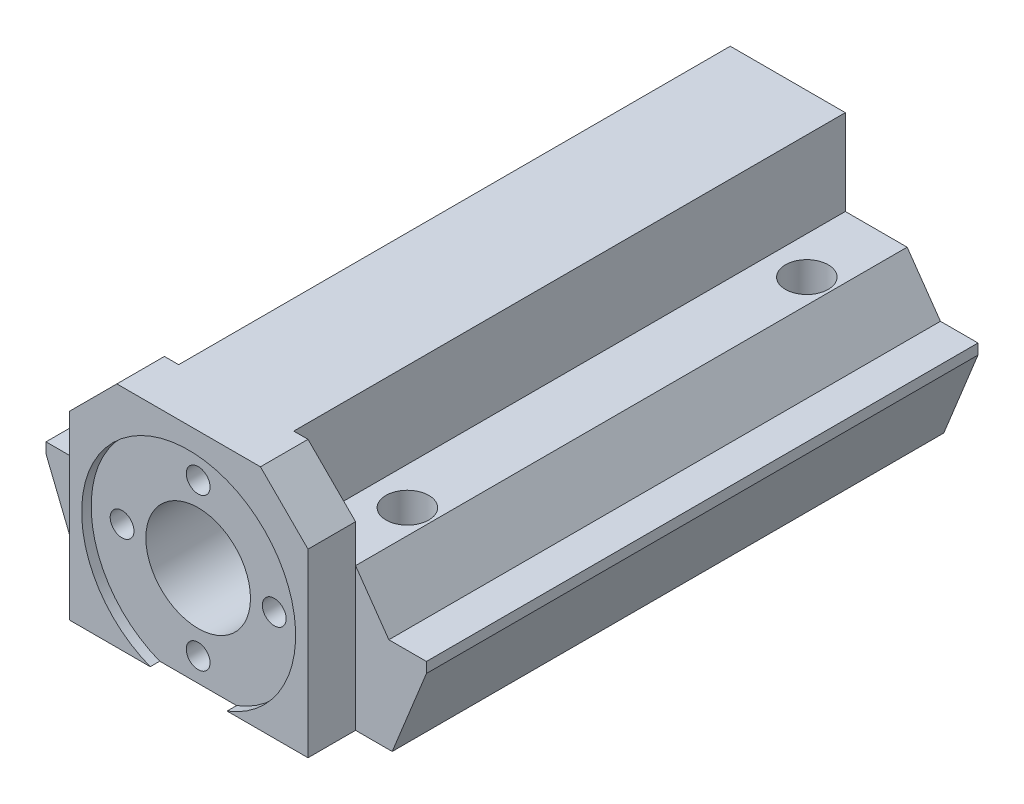
SolidWorks part; units mm, degrees
ref_plane "Front Plane" through (0, 0, 0) normal (0, 0, 1) x (1, 0, 0)
ref_plane "Top Plane" through (0, 0, 0) normal (0, 1, 0) x (1, 0, 0)
ref_plane "Right Plane" through (0, 0, 0) normal (1, 0, 0) x (0, 0, -1)
sketch "Sketch1" plane through (0, 0, 0) normal (0, 0, 1) x (1, 0, 0)
  line L0 (0, 0) -> (0, 14.7846) construction
  line L1 (-6.05, 25) -> (6.05, 25)
  line L2 (6.05, 25) -> (6.05, 16)
  line L3 (6.05, 16) -> (12.55, 16)
  line L4 (12.55, 16) -> (12.55, 0)
  line L5 (12.55, 0) -> (-12.55, 0)
  line L6 (-12.55, 16) -> (-12.55, 0)
  line L7 (-6.05, 16) -> (-12.55, 16)
  line L8 (-6.05, 25) -> (-6.05, 16)
  point P5 (0, 0)
  point P13 (0, 25)
  dimension "D1" = 12.1
  dimension "D2" = 6.5
  dimension "D3" = 16
  dimension "D4" = 9
extrude "Boss-Extrude1" add sketch "Sketch1" along normal blind 58
sketch "Sketch11" plane through (0, 0, 0) normal (0, 0, -1) x (-1, 0, 0)
  line L0 (-12.55, 0) -> (-12.55, 16) construction
  line L1 (-20, 11) -> (20, 11)
  line L2 (-20, 11) -> (-20, 0)
  line L3 (-20, 0) -> (20, 0)
  line L4 (20, 11) -> (20, 0)
  line L9 (12.55, 0) -> (-12.55, 0) construction
  dimension "D1" = 40
  dimension "D2" = 7.45
  dimension "D3" = 11
  dimension "D4" = 0
extrude "Boss-Extrude3" add sketch "Sketch11" against normal blind 58
sketch "Sketch5" plane through (0, 0, 58) normal (0, 0, 1) x (1, 0, 0)
  line L1 (-12.55, 0) -> (12.55, 0)
  line L2 (-12.55, 0) -> (-12.55, 25)
  line L3 (-12.55, 25) -> (12.55, 25)
  line L4 (12.55, 0) -> (12.55, 25)
  dimension "D1" = 25.1
  dimension "D2" = 25
extrude "Boss-Extrude2" add sketch "Sketch5" along normal blind 5
sketch "Sketch6" plane through (0, 0, 0) normal (0, 0, -1) x (-1, 0, 0)
  line L1 (20, 0) -> (-20, 0) construction
  circle A0 centre (0, 11.5) radius 5.5
  dimension "D1" = 11
  dimension "D2" = 11.5
extrude "Cut-Extrude4" cut sketch "Sketch6" against normal blind 63
sketch "Sketch7" plane through (0, 0, 63) normal (0, 0, 1) x (1, 0, 0)
  circle A0 centre (0, 11.5) radius 11.25
  dimension "D1" = 22.5
extrude "Cut-Extrude5" cut sketch "Sketch7" against normal blind 1
sketch "Sketch9" plane through (0, 0, 62) normal (0, 0, 1) x (1, 0, 0)
  circle A0 centre (-8, 11.5) radius 1.25
  circle A1 centre (8, 11.5) radius 1.25
  circle A2 centre (0, 3.5) radius 1.25
  circle A3 centre (0, 19.5) radius 1.25
  circle A4 centre (0, 11.5) radius 5.5 construction
  dimension "D1" = 2.5
  dimension "D2" = 2.5
  dimension "D3" = 2.5
  dimension "D4" = 2.5
  dimension "D9" = 0
  dimension "D5" = 8
  dimension "D6" = 8
  dimension "D7" = 8
  dimension "D8" = 8
  dimension "D10" = 0
sketch "Sketch10" plane through (0, 16, 0) normal (0, 1, 0) x (1, 0, 0)
  line L0 (-6.05, 0) -> (-12.55, 0) construction
  line L1 (12.55, 0) -> (6.05, 0) construction
  line L2 (-12.55, -58) -> (-12.55, 0) construction
  circle A0 centre (-10, -8) radius 2.25
  circle A1 centre (-10, -50) radius 2.25
  circle A2 centre (10, -50) radius 2.25
  circle A3 centre (10, -8) radius 2.25
  dimension "D1" = 4.5
  dimension "D2" = 4.5
  dimension "D3" = 4.5
  dimension "D4" = 4.5
  dimension "D5" = 42
  dimension "D6" = 42
  dimension "D7" = 8
  dimension "D8" = 8
  dimension "D9" = 20
  dimension "D10" = 20
  dimension "D11" = 2.55
  dimension "D12" = 2.55
extrude "Cut-Extrude7" cut sketch "Sketch10" against normal blind 16
chamfer "Chamfer2" distance 5 angle 45 2 edges at (-12.55, 25, 60.5) (12.55, 25, 60.5)
extrude "Cut-Extrude8" cut sketch "Sketch9" against normal blind 10
sketch "Sketch12" plane through (0, 0, 0) normal (0, -1, 0) x (1, 0, 0)
  line L0 (-12.55, 63) -> (12.55, 63) construction
  line L1 (12.1651, 46.25) -> (14.3301, 50)
  line L2 (14.3301, 50) -> (12.1651, 53.75)
  line L3 (12.1651, 53.75) -> (7.8349, 53.75)
  line L4 (7.8349, 53.75) -> (5.6699, 50)
  line L5 (5.6699, 50) -> (7.8349, 46.25)
  line L6 (7.8349, 46.25) -> (12.1651, 46.25)
  line L7 (-7.8349, 46.25) -> (-5.6699, 50)
  line L8 (-5.6699, 50) -> (-7.8349, 53.75)
  line L9 (-7.8349, 53.75) -> (-12.1651, 53.75)
  line L10 (-12.1651, 53.75) -> (-14.3301, 50)
  line L11 (-14.3301, 50) -> (-12.1651, 46.25)
  line L12 (-12.1651, 46.25) -> (-7.8349, 46.25)
  line L13 (-7.8349, 4.25) -> (-5.6699, 8)
  line L14 (-5.6699, 8) -> (-7.8349, 11.75)
  line L15 (-7.8349, 11.75) -> (-12.1651, 11.75)
  line L16 (-12.1651, 11.75) -> (-14.3301, 8)
  line L17 (-14.3301, 8) -> (-12.1651, 4.25)
  line L18 (-12.1651, 4.25) -> (-7.8349, 4.25)
  line L19 (12.1651, 4.25) -> (14.3301, 8)
  line L20 (14.3301, 8) -> (12.1651, 11.75)
  line L21 (12.1651, 11.75) -> (7.8349, 11.75)
  line L22 (7.8349, 11.75) -> (5.6699, 8)
  line L23 (5.6699, 8) -> (7.8349, 4.25)
  line L24 (7.8349, 4.25) -> (12.1651, 4.25)
  circle A0 centre (10, 50) radius 3.75 construction
  circle A1 centre (-10, 50) radius 3.75 construction
  circle A2 centre (-10, 8) radius 3.75 construction
  circle A3 centre (10, 8) radius 3.75 construction
  dimension "D1" = 7.5
  dimension "D2" = 7.5
  dimension "D3" = 7.5
  dimension "D4" = 7.5
extrude "Cut-Extrude9" cut sketch "Sketch12" against normal blind 8
chamfer "Chamfer4" distance 2 angle 45 24 edges at (-13.2476, 8, 6.125) (-13.2476, 8, 9.875) (-10, 8, 11.75) (-6.7524, 8, 9.875) (-6.7524, 8, 6.125) (-10, 8, 4.25) (6.7524, 8, 6.125) (6.7524, 8, 9.875) (10, 8, 11.75) (13.2476, 8, 9.875) (13.2476, 8, 6.125) (10, 8, 4.25) (6.7524, 8, 48.125) (6.7524, 8, 51.875) (10, 8, 53.75) (13.2476, 8, 51.875) (13.2476, 8, 48.125) (10, 8, 46.25) (-13.2476, 8, 48.125) (-13.2476, 8, 51.875) (-10, 8, 53.75) (-6.7524, 8, 51.875) (-6.7524, 8, 48.125) (-10, 8, 46.25)
chamfer "Chamfer6" distance 5 angle 35 2 edges
chamfer "Chamfer7" distance 4 angle 68 1 edges at (-20, 0, 29)
chamfer "Chamfer8" distance 4 angle 68 1 edges at (20, 0, 29)
sketch "Sketch13" plane through (0, 0, 0) normal (0, 0, -1) x (-1, 0, 0)
  line L1 (-20, 1) -> (20, 1)
  line L2 (-20, 1) -> (-20, -1)
  line L3 (-20, -1) -> (20, -1)
  line L4 (20, 1) -> (20, -1)
  line L5 (-20, 1) -> (20, -1) construction
  line L6 (-20, -1) -> (20, 1) construction
  point P0 (0, 0)
  dimension "D1" = 40
  dimension "D2" = 2
extrude "Cut-Extrude10" cut sketch "Sketch13" against normal blind 67
